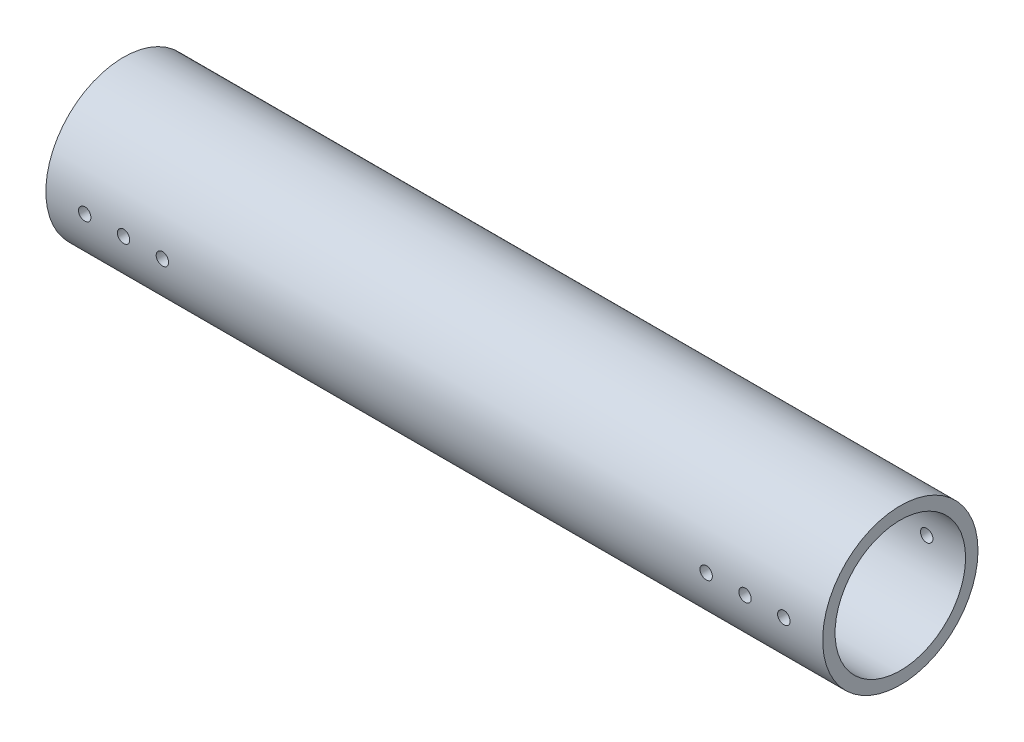
SolidWorks part; units mm, degrees
material "Zoltek Panex 33"
ref_plane "Спереди" through (0, 0, 0) normal (0, 0, 1) x (1, 0, 0)
ref_plane "Сверху" through (0, 0, 0) normal (0, 1, 0) x (1, 0, 0)
ref_plane "Справа" through (0, 0, 0) normal (1, 0, 0) x (0, 0, -1)
other "Configuration Table"
sketch "Эскиз2" plane through (0, 0, 0) normal (1, 0, 0) x (0, 0, -1)
  circle A0 centre (0, 0) radius 25
  circle A1 centre (0, 0) radius 21
  dimension "D1" = 50
  dimension "D2" = 42
extrude "Бобышка-Вытянуть2" add sketch "Эскиз2" along normal blind 250
ref_plane "Плоскость1" through (0, 0, 25) normal (0, 0, 1) x (1, 0, 0)
sketch "Эскиз4" plane through (0, 0, 25) normal (0, 0, 1) x (1, 0, 0)
  line L0 (0, -25) -> (250, -25) construction
  line L1 (250, -25) -> (250, 25) construction
  circle A0 centre (12.5, 0) radius 2
  circle A1 centre (237.5, 0) radius 2
  circle A2 centre (25, 0) radius 2
  circle A3 centre (37.5, 0) radius 2
  circle A4 centre (225, 0) radius 2
  circle A5 centre (212.5, 0) radius 2
  dimension "D1" = 4
  dimension "D4" = 4
  dimension "D6" = 4
  dimension "D8" = 4
  dimension "D10" = 4
  dimension "D11" = 4
  dimension "D2" = 12.5
  dimension "D3" = 25
  dimension "D5" = 12.5
  dimension "D7" = 12.5
  dimension "D9" = 12.5
  dimension "15" = 12.5
  dimension "D12" = 12.5
extrude "Вырез-Вытянуть2" cut sketch "Эскиз4" against normal through all and the other way blind 10 contours A0 | A1 | A2 | A3 | A5 | A4
equation "\"Diameter\"= 50мм"
equation "\"D1@Эскиз2\"= \"Diameter\""
equation "\"Length\" = 250мм"
equation "\"Thickness\"= 4мм"
equation "\"D1@Бобышка-Вытянуть2\"= \"Length\""
equation "\"D2@Эскиз2\" = \"Diameter\" - \"Thickness\" * 2"
equation "\"D4@Эскиз4\"=\"D1@Эскиз4\""
equation "\"D5@Эскиз4\"=\"D2@Эскиз4\""
equation "\"D3@Эскиз4\"=\"Diameter\"/2"
equation "\"D6@Эскиз4\"=\"D1@Эскиз4\""
equation "\"D8@Эскиз4\"=\"D6@Эскиз4\""
equation "\"D10@Эскиз4\"=\"D4@Эскиз4\""
equation "\"D11@Эскиз4\"=\"D4@Эскиз4\""
equation "\"D9@Эскиз4\"=\"D7@Эскиз4\""
